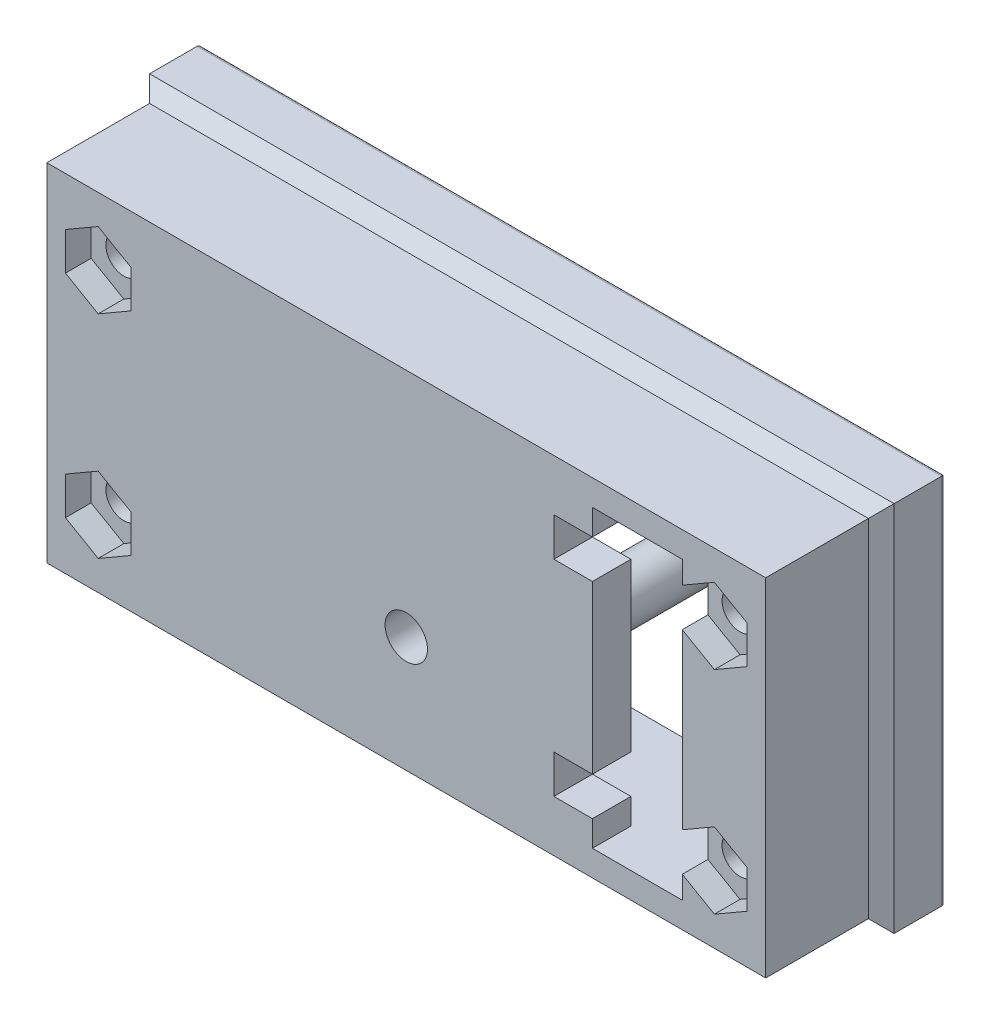
SolidWorks part; units mm, degrees
ref_plane "Front Plane" through (0, 0, 0) normal (0, 0, 1) x (1, 0, 0)
ref_plane "Top Plane" through (0, 0, 0) normal (0, 1, 0) x (1, 0, 0)
ref_plane "Right Plane" through (0, 0, 0) normal (1, 0, 0) x (0, 0, -1)
sketch "Sketch1" plane through (0, 0, 0) normal (0, 0, 1) x (1, 0, 0)
  line L1 (28, -13.5) -> (-28, -13.5)
  line L2 (28, -13.5) -> (28, 13.5)
  line L3 (28, 13.5) -> (-28, 13.5)
  line L4 (-28, -13.5) -> (-28, 13.5)
  line L5 (28, -13.5) -> (-28, 13.5) construction
  line L6 (28, 13.5) -> (-28, -13.5) construction
  line L7 (26, -11.5) -> (-26, -11.5)
  line L8 (26, -11.5) -> (26, 11.5)
  line L9 (26, 11.5) -> (-26, 11.5)
  line L10 (-26, -11.5) -> (-26, 11.5)
  line L11 (26, -11.5) -> (-26, 11.5) construction
  line L12 (26, 11.5) -> (-26, -11.5) construction
  point P0 (0, 0)
  point P6 (0, 0)
  dimension "D1" = 52
  dimension "D2" = 23
  dimension "D3" = 2
  dimension "D4" = 2
extrude "Boss-Extrude1" add sketch "Sketch1" along normal blind 8
sketch "Sketch2" plane through (0, 0, 8) normal (0, 0, 1) x (1, 0, 0)
  line L1 (28, -13.5) -> (-28, -13.5)
  line L2 (28, -13.5) -> (28, 13.5)
  line L3 (28, 13.5) -> (-28, 13.5)
  line L4 (-28, -13.5) -> (-28, 13.5)
  line L5 (28, -13.5) -> (-28, 13.5) construction
  line L6 (28, 13.5) -> (-28, -13.5) construction
  point P0 (0, 0)
extrude "Boss-Extrude2" add sketch "Sketch2" along normal blind 3
sketch "Sketch4" plane through (0, 0, 8) normal (0, 0, -1) x (-1, 0, 0)
  line L0 (26, -11.5) -> (-26, -11.5) construction
  line L1 (-21.5, 11.5) -> (-14.5, 11.5)
  line L2 (-21.5, 11.5) -> (-21.5, -11.5)
  line L3 (-21.5, -11.5) -> (-14.5, -11.5)
  line L4 (-14.5, 11.5) -> (-14.5, -11.5)
  line L5 (26, 11.5) -> (26, -11.5) construction
  line L6 (-26, 11.5) -> (26, 11.5) construction
  dimension "D1" = 7
  dimension "D2" = 40.5
extrude "Cut-Extrude1" cut sketch "Sketch4" against normal blind 3
sketch "Sketch5" plane through (0, 0, 8) normal (0, 0, -1) x (-1, 0, 0)
  circle A0 centre (-10, 0) radius 2
  dimension "D1" = 4
  dimension "D2" = 10
extrude "Boss-Extrude3" add sketch "Sketch5" along normal blind 9.7
fillet "Fillet1" radius 2 1 edges at (12, 0, 8)
sketch "Sketch6" plane through (0, 0, 8) normal (0, 0, -1) x (-1, 0, 0)
  line L0 (24, 8.25) -> (24, -8.25) construction
  line L1 (26, 11.5) -> (26, -11.5) construction
  line L2 (-24, 8.25) -> (-24, -8.25) construction
  line L3 (-26, -11.5) -> (-26, 11.5) construction
  line L4 (-28, -13.5) -> (-28, 13.5) construction
  circle A0 centre (24, 8.25) radius 1.4
  circle A1 centre (24, -8.25) radius 1.4
  circle A2 centre (-24, 8.25) radius 1.4
  circle A3 centre (-24, -8.25) radius 1.4
  point P4 (24, 0)
  point P6 (0, 0)
  point P17 (-24, 0)
  dimension "D2" = 2.8
  dimension "D3" = 2.8
  dimension "D4" = 2
  dimension "D5" = 16.5
  dimension "D6" = 4
  dimension "D1" = 16.5
extrude "Cut-Extrude2" cut sketch "Sketch6" against normal blind 10
sketch "Sketch8" plane through (0, 0, 11) normal (0, 0, 1) x (1, 0, 0)
  line L1 (-26.55, 9.7222) -> (-26.55, 6.7778)
  line L2 (-26.55, 6.7778) -> (-24, 5.3055)
  line L3 (-24, 5.3055) -> (-21.45, 6.7778)
  line L4 (-21.45, 6.7778) -> (-21.45, 9.7222)
  line L5 (-21.45, 9.7222) -> (-24, 11.1945)
  line L6 (-24, 11.1945) -> (-26.55, 9.7222)
  line L7 (-24, -5.3055) -> (-26.55, -6.7778)
  line L8 (-26.55, -6.7778) -> (-26.55, -9.7222)
  line L9 (-26.55, -9.7222) -> (-24, -11.1945)
  line L10 (-24, -11.1945) -> (-21.45, -9.7222)
  line L11 (-21.45, -9.7222) -> (-21.45, -6.7778)
  line L12 (-21.45, -6.7778) -> (-24, -5.3055)
  line L13 (24, 11.1945) -> (21.45, 9.7222)
  line L14 (-28, 13.5) -> (-28, -13.5) construction
  line L15 (21.45, 9.7222) -> (21.45, 6.7778)
  line L16 (21.45, 6.7778) -> (24, 5.3055)
  line L17 (24, 5.3055) -> (26.55, 6.7778)
  line L18 (26.55, 6.7778) -> (26.55, 9.7222)
  line L19 (26.55, 9.7222) -> (24, 11.1945)
  line L20 (24, -5.3055) -> (21.45, -6.7778)
  line L21 (21.45, -6.7778) -> (21.45, -9.7222)
  line L22 (21.45, -9.7222) -> (24, -11.1945)
  line L23 (24, -11.1945) -> (26.55, -9.7222)
  line L24 (26.55, -9.7222) -> (26.55, -6.7778)
  line L25 (26.55, -6.7778) -> (24, -5.3055)
  circle A0 centre (-24, 8.25) radius 2.55 construction
  circle A1 centre (-24, -8.25) radius 2.55 construction
  circle A2 centre (24, 8.25) radius 2.55 construction
  circle A3 centre (24, -8.25) radius 2.55 construction
  dimension "D2" = 5.1
extrude "Cut-Extrude3" cut sketch "Sketch8" against normal blind 2
sketch "Sketch10" plane through (0, 0, 8) normal (0, 0, -1) x (-1, 0, 0)
  line L1 (26, 11.5) -> (17.3098, 11.5)
  line L2 (26, 11.5) -> (26, 3.9581)
  line L3 (26, 3.9581) -> (17.3098, 3.9581)
  line L4 (17.3098, 11.5) -> (17.3098, 3.9581)
  line L5 (26, -11.5) -> (16.8129, -11.5)
  line L6 (26, -11.5) -> (26, -4.0462)
  line L7 (26, -4.0462) -> (16.8129, -4.0462)
  line L8 (16.8129, -11.5) -> (16.8129, -4.0462)
  line L9 (-26, 11.5) -> (-20.6838, 11.5)
  line L10 (-26, 11.5) -> (-26, 4.9094)
  line L11 (-26, 4.9094) -> (-20.6838, 4.9094)
  line L12 (-20.6838, 11.5) -> (-20.6838, 4.9094)
  line L13 (-26, -11.5) -> (-20.0802, -11.5)
  line L14 (-26, -11.5) -> (-26, -4.507)
  line L15 (-26, -4.507) -> (-20.0802, -4.507)
  line L16 (-20.0802, -11.5) -> (-20.0802, -4.507)
  circle A0 centre (24, 8.25) radius 1.4
  circle A1 centre (24, -8.25) radius 1.4
  circle A2 centre (24, -8.25) radius 2.4
  circle A3 centre (24, 8.25) radius 2.4
  circle A4 centre (24, 8.25) radius 1.4 construction
  circle A5 centre (-24, 8.25) radius 1.4
  circle A6 centre (-24, 8.25) radius 2.4
  circle A7 centre (-24, -8.25) radius 1.4
  circle A8 centre (-24, -8.25) radius 2.4
  circle M13 centre (24, 8.25) radius 1.4
  circle M14 centre (24, -8.25) radius 1.4
  dimension "D1" = 1
  dimension "D2" = 1
sketch "Sketch11" plane through (0, 0, 8) normal (0, 0, -1) x (-1, 0, 0)
  line L0 (-14.5, -11.5) -> (-14.5, 11.5) construction
  line L1 (-14.5, 9.5) -> (-11.5, 9.5)
  line L2 (-14.5, 9.5) -> (-14.5, 6.5)
  line L3 (-14.5, 6.5) -> (-11.5, 6.5)
  line L4 (-11.5, 9.5) -> (-11.5, 6.5)
  line L5 (-26, 11.5) -> (26, 11.5) construction
  line L6 (-14.5, -6.5) -> (-11.5, -6.5)
  line L7 (-14.5, -6.5) -> (-14.5, -9.5)
  line L8 (-14.5, -9.5) -> (-11.5, -9.5)
  line L9 (-11.5, -6.5) -> (-11.5, -9.5)
  line L10 (26, -11.5) -> (-14.5, -11.5) construction
  line L13 (28, -13.5) -> (-28, -13.5) construction
  circle A0 centre (0, -4.5) radius 1.65
  dimension "D1" = 3.3
  dimension "D6" = 9
  dimension "D2" = 3
  dimension "D3" = 3
  dimension "D4" = 2
  dimension "D5" = 2
extrude "Cut-Extrude4" cut sketch "Sketch11" against normal blind 10
extrude "Boss-Extrude5" add sketch "Sketch10" along normal blind 10 contours L2 A3 M13 | L6 A2 M14 region at (-25.9349, 8.25, 8) region at (-21.6651, -8.25, 8)
extrude "Boss-Extrude6" add sketch "Sketch10<5>" along normal blind 12.5 contours L10 A6 A5 | L14 A8 A7 region at (23.326, 10.4855, 8) region at (25.9349, -8.25, 8)
sketch "Sketch10<5>" plane through (0, 0, 8) normal (0, 0, -1) x (-1, 0, 0) same geometry as "Sketch10"
sketch "Sketch12" plane through (0, 0, 0) normal (0, 0, -1) x (-1, 0, 0)
  line L1 (-28, 13.5) -> (28, 13.5)
  line L2 (-28, 13.5) -> (-28, -13.5)
  line L3 (-28, -13.5) -> (28, -13.5)
  line L4 (28, 13.5) -> (28, -13.5)
  line L5 (-29, 14.5) -> (29, 14.5)
  line L6 (-29, 14.5) -> (-29, -14.5)
  line L7 (-29, -14.5) -> (29, -14.5)
  line L8 (29, 14.5) -> (29, -14.5)
  dimension "D1" = 1
  dimension "D2" = 1
  dimension "D3" = 1
  dimension "D4" = 1
extrude "Boss-Extrude7" add sketch "Sketch12" along normal blind 2 and the other way blind 2
sketch "Sketch14" plane through (0, 0, 8) normal (0, 0, -1) x (-1, 0, 0)
  line L0 (-14.5, -6.5) -> (-14.5, 6.5) construction
  line L1 (0, -1.2668) -> (-2.8, -2.8834)
  line L2 (-2.8, -2.8834) -> (-2.8, -6.1166)
  line L3 (-2.8, -6.1166) -> (0, -7.7332)
  line L4 (0, -7.7332) -> (2.8, -6.1166)
  line L5 (2.8, -6.1166) -> (2.8, -2.8834)
  line L6 (2.8, -2.8834) -> (0, -1.2668)
  line L7 (0, 1.0426) -> (-4.8, -1.7287)
  line L8 (-4.8, -1.7287) -> (-4.8, -7.2713)
  line L9 (-4.8, -7.2713) -> (0, -10.0426)
  line L10 (0, -10.0426) -> (4.8, -7.2713)
  line L11 (4.8, -7.2713) -> (4.8, -1.7287)
  line L12 (4.8, -1.7287) -> (0, 1.0426)
  circle A0 centre (0, -4.5) radius 2.8 construction
  circle A1 centre (0, -4.5) radius 4.8 construction
  dimension "D1" = 5.6
  dimension "D2" = 2
extrude "Boss-Extrude8" add sketch "Sketch14" along normal blind 3
fillet "Fillet2" radius 0.3 8 edges at (-28, 0, -2) (0, 13.5, -2) (28, 0, -2) (0, -13.5, -2) (0, 14.5, -2) (-29, 0, -2) (0, -14.5, -2) (29, 0, -2)
fillet "Fillet3" radius 0.3 13 edges at (8, 0, -1.7) (-21.6, -8.25, -2) (-26, -8.25, -2) (-25.4, -8.25, -2) (-21.6, 8.25, -2) (-26, 8.25, -2) (-25.4, 8.25, -2) (21.6, 8.25, -4.5) (26, 8.25, -4.5) (22.6, 8.25, -4.5) (21.6, -8.25, -4.5) (26, -8.25, -4.5) (22.6, -8.25, -4.5)
chamfer "Chamfer1" distance 1 angle 45 4 edges at (0, -13.5, 2) (28, 0, 2) (-28, 0, 2) (0, 13.5, 2)
